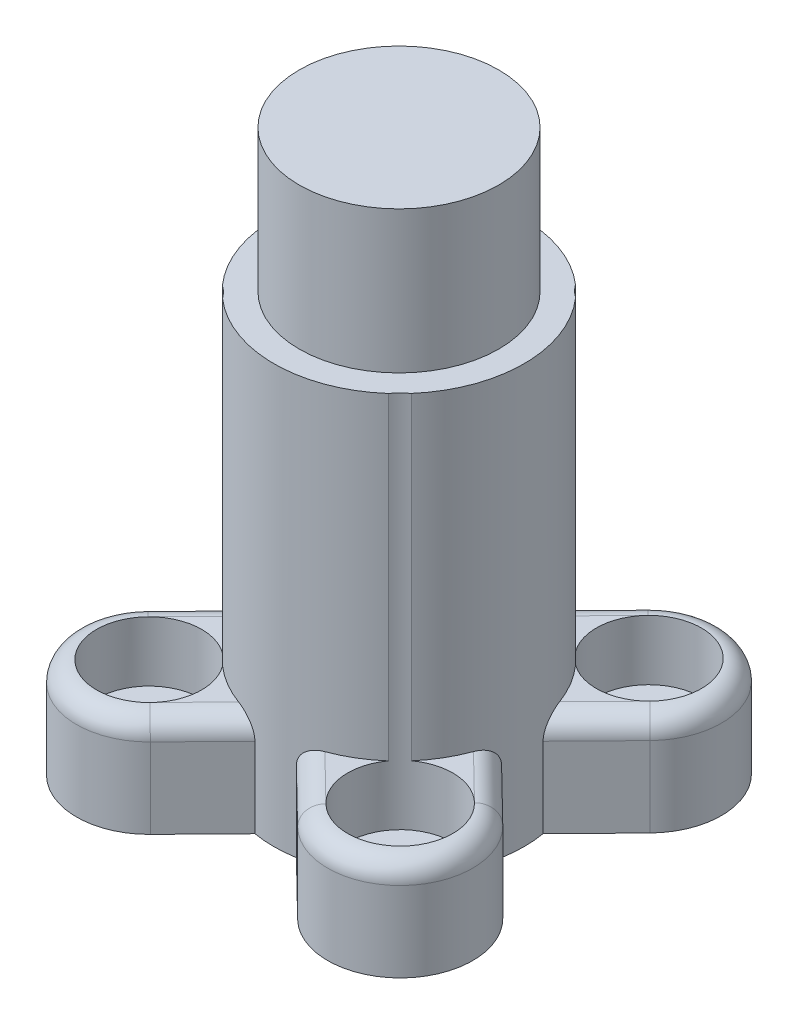
SolidWorks part; units mm, degrees
ref_plane "Front Plane" through (0, 0, 0) normal (0, 0, 1) x (1, 0, 0)
ref_plane "Top Plane" through (0, 0, 0) normal (0, 1, 0) x (1, 0, 0)
ref_plane "Right Plane" through (0, 0, 0) normal (1, 0, 0) x (0, 0, -1)
sketch "Sketch1" plane through (0, 0, 0) normal (0, 1, 0) x (1, 0, 0)
  circle A0 centre (0, 0) radius 9.97
  dimension "D1" = 19.94
extrude "Boss-Extrude1" add sketch "Sketch1" along normal blind 16
sketch "Sketch3" plane through (0, 0, 0) normal (0, -1, 0) x (1, 0, 0)
  circle A0 centre (0, 0) radius 12.5
  point P2 (0, 0)
  dimension "D1" = 25
extrude "Boss-Extrude2" add sketch "Sketch3" against normal blind 1.8 and the other way blind 40
shell "Shell2" thickness 4 removed face at (0, -40, -12.5)
sketch "Sketch5" plane through (0, -40, 0) normal (0, -1, 0) x (1, 0, 0)
  line L0 (0, 0) -> (19.9596, 0) construction
  line L1 (0, 0) -> (0, 20.8827) construction
  line L2 (0, 0) -> (12.5474, 12.4273) construction
  line L3 (17.6151, 7.2425) -> (12.3268, 2.0737)
  line L4 (7.4792, 17.6114) -> (2.0737, 12.3268)
  circle A0 centre (12.5474, 12.4273) radius 3.25
  circle A1 centre (12.5474, 12.4273) radius 5.25
  arc A2 (17.6151, 7.2425) -> (7.4792, 17.6114) centre (12.5474, 12.4273) ccw
  circle A3 centre (0, 0) radius 12.5 construction
  circle A5 centre (12.5474, 12.4273) radius 7.25 construction
  circle A8 centre (0, 0) radius 12.5
  arc A9 (12.3268, 2.0737) -> (2.0737, 12.3268) centre (0, 0) ccw
  circle M3 centre (0, 0) radius 12.5
  dimension "D2" = 6.5
  dimension "D3" = 10.5
  dimension "D1" = 17.66
  dimension "D4" = 2
  dimension "D5" = 0
sketch "Sketch6" plane through (0, -40, 0) normal (0, -1, 0) x (1, 0, 0)
  circle A0 centre (0, 0) radius 25
  circle A1 centre (0, 0) radius 12.5
  dimension "D1" = 50
extrude "Boss-Extrude3" add sketch "Sketch5" against normal blind 10 contours L3 A2 L4 A1 M3 region at (14.7963, -40, 4.8368)
extrude "Boss-Extrude4" add sketch "Sketch5<3>" against normal blind 4 contours A1 A0 M3 region at (8.9868, -40, 8.9007)
sketch "Sketch5<3>" plane through (0, -40, 0) normal (0, -1, 0) x (1, 0, 0) same geometry as "Sketch5"
sketch "Sketch7" plane through (0, -36, 0) normal (0, 1, 0) x (1, 0, 0)
  circle A0 centre (12.5474, -12.4273) radius 5.25
extrude "Cut-Extrude3" cut sketch "Sketch7" along normal up to surface (52 mm away) up to face at (0, 16, 9.97)
pattern_circular "CirPattern1" count 4 every 90 about axis through (0, -40, 0) along (0, 1, 0) of "Boss-Extrude3", "Boss-Extrude4", "Cut-Extrude3"
fillet "Fillet1" radius 2 12 edges at (4.6581, -30, -14.9709) (14.9691, -30, -4.7765) (-14.9709, -30, -4.6581) (-4.7765, -30, -14.9691) (14.9709, -30, 4.6581) (4.7765, -30, 14.9691) (-4.6581, -30, 14.9709) (-14.9691, -30, 4.7765) (17.4952, -30, -17.7319) (-17.7319, -30, -17.4952) (17.7319, -30, 17.4952) (-17.4952, -30, 17.7319)
